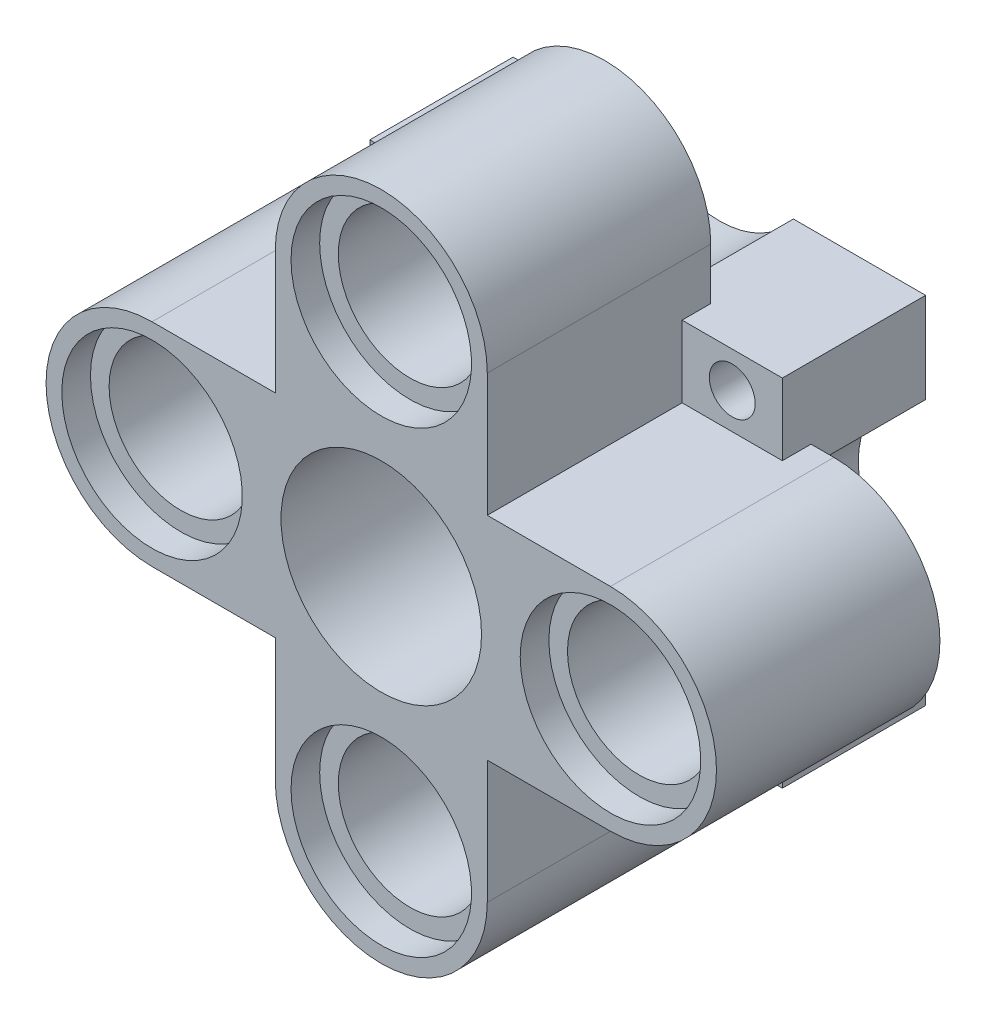
SolidWorks part; units mm, degrees
ref_plane "前视基准面" through (0, 0, 0) normal (0, 0, 1) x (1, 0, 0)
ref_plane "上视基准面" through (0, 0, 0) normal (0, 1, 0) x (1, 0, 0)
ref_plane "右视基准面" through (0, 0, 0) normal (1, 0, 0) x (0, 0, -1)
other "Configuration Table"
sketch "草图2" plane through (0, 0, 0) normal (0, 0, 1) x (1, 0, 0)
  line L0 (-8, 0) -> (8, 0) construction
  line L2 (-11.7, -3.7) -> (11.7, -3.7)
  line L3 (-11.7, -3.7) -> (-11.7, 3.7)
  line L4 (-11.7, 3.7) -> (11.7, 3.7)
  line L5 (11.7, -3.7) -> (11.7, 3.7)
  line L6 (-11.7, -3.7) -> (11.7, 3.7) construction
  line L7 (-11.7, 3.7) -> (11.7, -3.7) construction
  line L8 (-3.7, 11.7) -> (3.7, 11.7)
  line L9 (-3.7, 11.7) -> (-3.7, -11.7)
  line L10 (-3.7, -11.7) -> (3.7, -11.7)
  line L11 (3.7, 11.7) -> (3.7, -11.7)
  line L12 (-3.7, 11.7) -> (3.7, -11.7) construction
  line L13 (-3.7, -11.7) -> (3.7, 11.7) construction
  circle A0 centre (0, 0) radius 3.5
  circle A1 centre (-8, 0) radius 2.5
  circle A2 centre (8, 0) radius 2.5
  circle A3 centre (8, 0) radius 3.15
  circle A4 centre (-8, 0) radius 3.15
  circle A5 centre (-8, 0) radius 3.7
  circle A6 centre (8, 0) radius 3.7
  circle A7 centre (0, 8) radius 2.5
  circle A8 centre (0, 8) radius 3.15
  circle A9 centre (0, 8) radius 3.7
  circle A10 centre (0, -8) radius 2.5
  circle A11 centre (0, -8) radius 3.15
  circle A12 centre (0, -8) radius 3.7
  point P15 (0, 0)
  dimension "D2" = 5
  dimension "D3" = 7
  dimension "D4" = 6.3
  dimension "D1" = 8
  dimension "D5" = 7.4
extrude "凸台-拉伸1" add sketch "草图2" along normal blind 7.8 contours L4 L5 L2 L3 | L8 L11 L10 L9
sketch "草图3" plane through (0, 0, 0) normal (0, 0, -1) x (-1, 0, 0)
  line L1 (-7.2, 6.2) -> (7.2, 6.2)
  line L2 (-7.2, 6.2) -> (-7.2, -6.2)
  line L3 (-7.2, -6.2) -> (7.2, -6.2)
  line L4 (7.2, 6.2) -> (7.2, -6.2)
  line L5 (-7.2, 6.2) -> (7.2, -6.2) construction
  line L6 (-7.2, -6.2) -> (7.2, 6.2) construction
  line L7 (-7.2, 3.7) -> (7.2, 3.7)
  line L8 (-7.2, 3.7) -> (-7.2, -3.7)
  line L9 (-7.2, -3.7) -> (7.2, -3.7)
  line L10 (7.2, 3.7) -> (7.2, -3.7)
  line L11 (-7.2, 3.7) -> (7.2, -3.7) construction
  line L12 (-7.2, -3.7) -> (7.2, 3.7) construction
  point P0 (0, 0)
  point P7 (0, 0)
  dimension "D1" = 14.4
  dimension "D2" = 12.4
  dimension "D3" = 7.4
extrude "凸台-拉伸2" add sketch "草图3" along normal blind 5 from offset 1 contours L1 L4 L3 L2 offset against normal yes
extrude "切除-拉伸3" cut sketch "草图2<6>" along normal through all contours A9 L8 L9 | A9 L11 L8 | A6 L5 L4 | A6 L2 L5 | A12 L10 L11 | A12 L9 L10 | A5 L3 L2 | A5 L4 L3 | A7 | A1 | A0 | A2 | A10 region at (-10.8735, -2.8735, 0) region at (-10.8735, 2.8735, 0) region at (-2.8735, -10.8735, 0) region at (10.8735, -2.8735, 0) region at (2.8735, -10.8735, 0) region at (-2.8735, 10.8735, 0) region at (10.8735, 2.8735, 0) region at (2.8735, 10.8735, 0)
sketch "草图2<6>" plane through (0, 0, 0) normal (0, 0, 1) x (1, 0, 0) same geometry as "草图2"
extrude "切除-拉伸1" cut sketch "草图2<3>" along normal blind 1 contours A4 | A8 | A3 | A11
sketch "草图2<3>" plane through (0, 0, 0) normal (0, 0, 1) x (1, 0, 0) same geometry as "草图2"
extrude "切除-拉伸2" cut sketch "草图2<5>" against normal blind 1 from surface contours A4 | A11 | A3 | A8 starting at face at (-5.5, 0, 7.8)
sketch "草图2<5>" plane through (0, 0, 0) normal (0, 0, 1) x (1, 0, 0) same geometry as "草图2"
sketch "草图4" plane through (0, 0, -4) normal (0, 0, -1) x (-1, 0, 0)
  line L0 (7.2, 6.2) -> (3.7, 3.7) construction
  line L1 (-3.7, -3.7) -> (-7.2, -6.2) construction
  line L3 (7.2, 6.2) -> (7.2, -6.2) construction
  line L4 (-7.2, 6.2) -> (7.2, 6.2) construction
  circle A0 centre (5.45, 4.95) radius 0.8
  circle A1 centre (-5.45, 4.95) radius 0.8
  circle A2 centre (5.45, -4.95) radius 0.8
  circle A3 centre (-5.45, -4.95) radius 0.8
  dimension "D1" = 1.6
  dimension "D2" = 1.75
  dimension "D3" = 1.25
extrude "切除-拉伸4" cut sketch "草图4" against normal through all contours A0 | A1 | A3 | A2
extrude "切除-拉伸5" cut sketch "草图2<7>" against normal through all contours A8 | A3 | A0 | A11 | A4
sketch "草图2<7>" plane through (0, 0, 0) normal (0, 0, 1) x (1, 0, 0) same geometry as "草图2"
